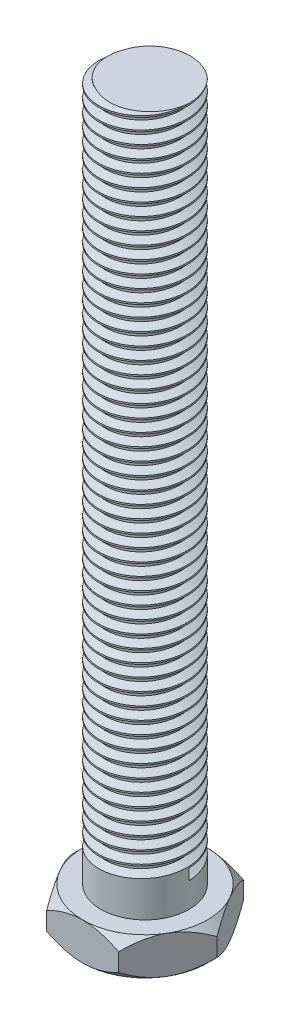
SolidWorks part; units mm, degrees
ref_plane "Front Plane" through (0, 0, 0) normal (0, 0, 1) x (1, 0, 0)
ref_plane "Top Plane" through (0, 0, 0) normal (0, 1, 0) x (1, 0, 0)
ref_plane "Right Plane" through (0, 0, 0) normal (1, 0, 0) x (0, 0, -1)
sketch "Sketch1" plane through (0, 0, 0) normal (0, 1, 0) x (1, 0, 0)
  line L1 (2.8868, 0) -> (1.4434, 2.5)
  line L2 (1.4434, 2.5) -> (-1.4434, 2.5)
  line L3 (-1.4434, 2.5) -> (-2.8868, 0)
  line L4 (-2.8868, 0) -> (-1.4434, -2.5)
  line L5 (-1.4434, -2.5) -> (1.4434, -2.5)
  line L6 (1.4434, -2.5) -> (2.8868, 0)
  circle A1 centre (0, 0) radius 2.5 construction
  dimension "D1" = 5
extrude "Boss-Extrude1" add sketch "Sketch1" along normal mid plane 1.5
sketch "Sketch2" plane through (0, 0.75, 0) normal (0, 1, 0) x (1, 0, 0)
  line L0 (1.4434, 2.5) -> (-1.4434, 2.5) construction
  circle A0 centre (0, 0) radius 2.5
extrude "Cut-Extrude2" cut sketch "Sketch2" against normal through all draft 45 flip side to cut
mirror "Mirror1" about plane through (0, 0, 0) normal (0, 1, 0) of "Cut-Extrude2" second plane through (0, 0, 0) second plane normal (0, 0, 1)
sketch "Sketch3" plane through (0, 0.75, 0) normal (0, 1, 0) x (1, 0, 0)
  circle A0 centre (0, 0) radius 1.77
  dimension "D1" = 3.54
extrude "Boss-Extrude2" add sketch "Sketch3" along normal blind 28
thread "Thread1" pitch 0.5 method cut profile "Thread Profile1" start angle 0, offset 1, length 0, pitch 0.5, diameter 3.54
ref_plane "Plane1" through (1.77, 1.75, 0) normal (0, 0, 1) x (1, 0, 0)
sketch "Thread Profile1" plane through (1.77, 1.75, 0) normal (0, 0, 1) x (1, 0, 0)
  line L0 (0, 0) -> (0, 0.5) construction
  line L11 (0, 0) -> (0, 0.4375)
  line L12 (0, 0.4375) -> (-0.2706, 0.2812)
  line L13 (-0.2706, 0.2812) -> (-0.2706, 0.1562)
  line L15 (-0.2706, 0.1562) -> (0, 0)
  line L17 (-0.2706, 0.2187) -> (0, 0.2187) construction
  point P2 (0, 0)
  dimension "Pitch" = 0.5
  dimension "Profile_Angle" = 60
  dimension "Profile_Land" = 0.125
  dimension "Profile_Height" = 0.2706
equation "\"Bolt shaft dia\"= 3.54mm"
equation "\"bolt head dia\"= 5mm"
equation "\"bolt head thickness\"= 1.5mm"
equation "\"Bolt shaft length\"= 28mm"
equation "\"D1@Sketch1\"=\"bolt head dia\""
equation "\"D1@Boss-Extrude1\"=\"bolt head thickness\""
equation "\"D1@Sketch3\"=\"Bolt shaft dia\""
equation "\"D1@Boss-Extrude2\"=\"Bolt shaft length\""
